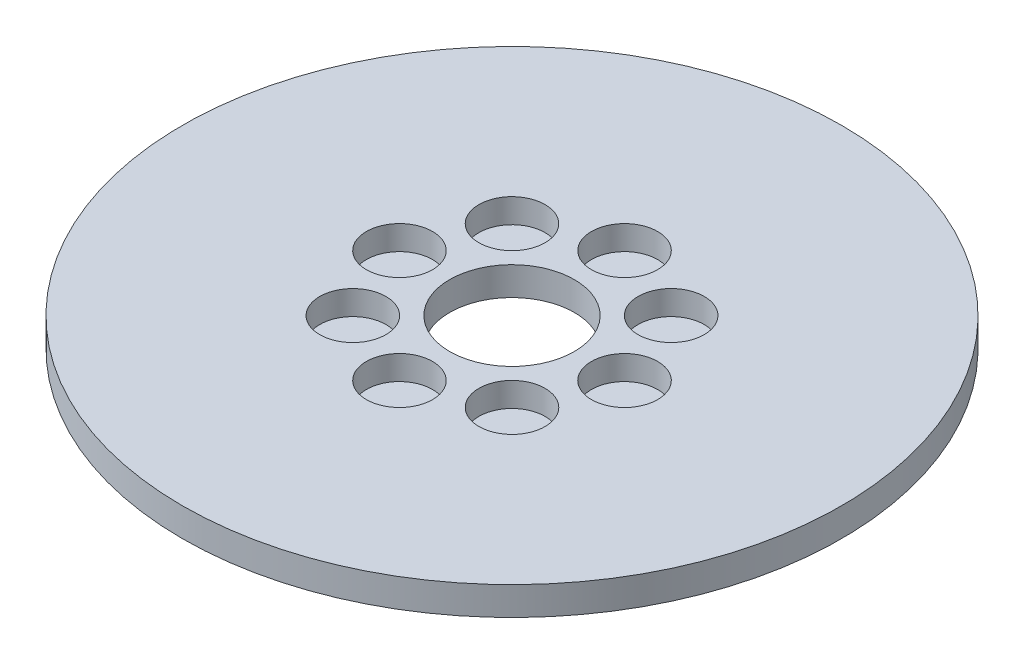
SolidWorks part; units mm, degrees
ref_plane "Front Plane" through (0, 0, 0) normal (0, 0, 1) x (1, 0, 0)
ref_plane "Top Plane" through (0, 0, 0) normal (0, 1, 0) x (1, 0, 0)
ref_plane "Right Plane" through (0, 0, 0) normal (1, 0, 0) x (0, 0, -1)
sketch "Sketch1" plane through (0, 0, 0) normal (0, 1, 0) x (1, 0, 0)
  circle A0 centre (0, 0) radius 92.5
  dimension "FLANGE_OD" = 185
extrude "Boss-Extrude1" add sketch "Sketch1" along normal blind 8
sketch "Sketch2" plane through (0, 0, 0) normal (0, 1, 0) x (1, 0, 0)
  circle A0 centre (0, 0) radius 17.5
  dimension "BORE_D" = 35
extrude "Cut-Extrude1" cut sketch "Sketch2" along normal through all
sketch "Sketch3" plane through (0, 8, 0) normal (0, 1, 0) x (1, 0, 0)
  circle A0 centre (0, 0) radius 31.5867 construction
  circle A1 centre (-31.5867, 0) radius 9.2893
  dimension "BOLT_D" = 18.5786
  dimension "BOLT_PCD" = 63.1733
extrude "Cut-Extrude2" cut sketch "Sketch3" against normal blind 6.8234
pattern_circular "CirPattern1" count 8 over 360 about axis through (0, 0, 0) along (0, 1, 0) of "Cut-Extrude2"
